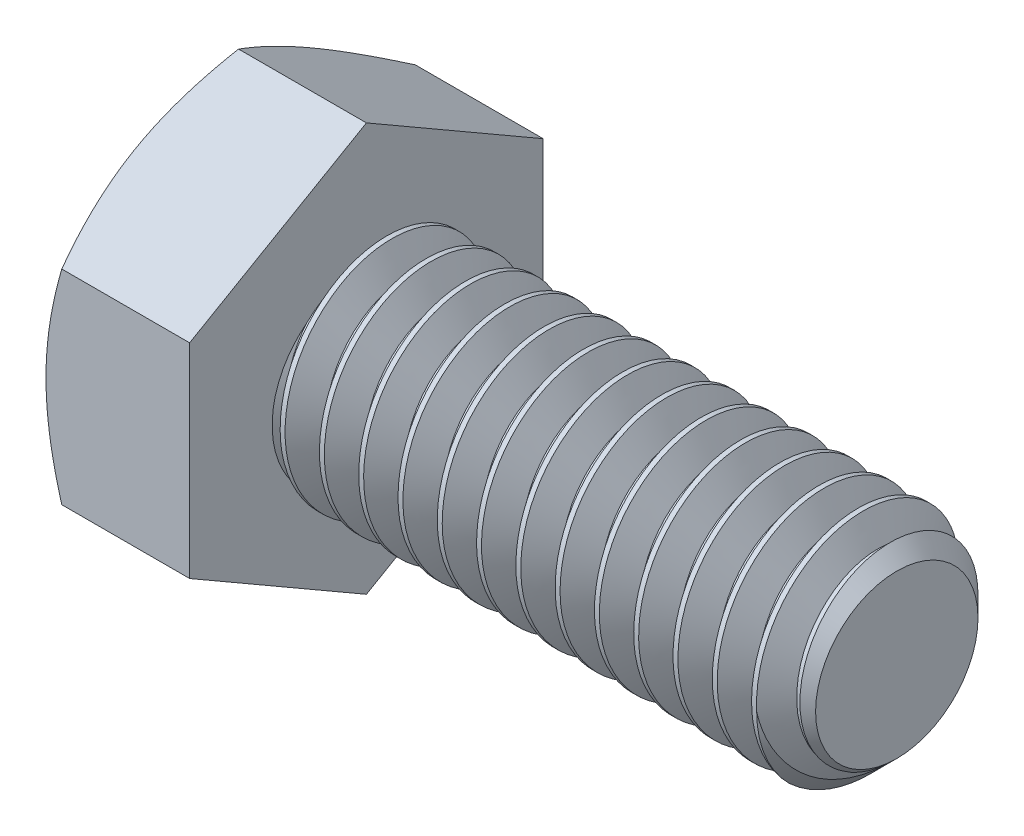
SolidWorks part; units mm, degrees
note: '?' marks a value the reader was unsure of.
ref_plane "Front Plane" through (0, 0, 0) normal (0, 0, 1) x (1, 0, 0)
ref_plane "Top Plane" through (0, 0, 0) normal (0, 1, 0) x (1, 0, 0)
ref_plane "Right Plane" through (0, 0, 0) normal (1, 0, 0) x (0, 0, -1)
sketch "Sketch1" plane through (0, 0, 0) normal (0, 0, 1) x (1, 0, 0)
  line L0 (-12.1047, 0) -> (12.1047, 0) construction
  line L1 (12.1047, 3.9751) -> (12.1047, -3.9751) construction
  line L2 (-6.9453, 6.35) -> (-6.9453, -6.35) construction
  line L3 (-12.1047, 6.35) -> (-12.1047, -6.35) construction
  line L4 (12.1047, 3.9751) -> (13.5158, 3.9751)
  point P9 (-6.9453, 0)
  point P10 (7.1658, -3.9751)
  point P12 (-12.1047, 6.35)
  point P13 (-6.9453, 6.35)
  point P14 (12.1047, 3.9751)
  dimension "Screw Size Decimal Equivalent" = 7.9502
  dimension "Head Width" = 12.7
  dimension "Head Height" = 5.1594
  dimension "Length" = 19.05
  dimension "D1" = 4.9389
  dimension "Thread Size" = 7.9502
  dimension "Pitch" = 1.4111
ref_plane "Plane2" through (12.1047, 0, 0) normal (1, 0, 0) x (0, 0, -1)
sketch "Sketch5" plane through (12.1047, 0, 0) normal (1, 0, 0) x (0, 0, -1)
  circle A0 centre (0, 0) radius 3.9751
extrude "Boss-Extrude3" add sketch "Sketch5" against normal up to vertex (19.05 mm away) up to point (-6.9453, 0, 0)
sketch "Sketch9" plane through (12.1047, 0, 0) normal (1, 0, 0) x (0, 0, -1)
  circle A1 centre (0, 0) radius 3.9751
  circle A2 centre (0, 0) radius 3.9751
  dimension "D1" = 0
curve "Helix/Spiral1" pitch 1.4111 height 20.4611 turns 14.5 parameters "Pitch"=1.4111
chamfer "Chamfer1" distance 1.0583 angle 45 1 edges at (12.1047, 0, -3.9751)
sketch "Sketch11" plane through (-6.9453, 0, 0) normal (-1, 0, 0) x (0, 0, 1)
  line L1 (0, 7.3323) -> (-6.35, 3.6662)
  line L2 (-6.35, 3.6662) -> (-6.35, -3.6662)
  line L3 (-6.35, -3.6662) -> (0, -7.3323)
  line L4 (0, -7.3323) -> (6.35, -3.6662)
  line L5 (6.35, -3.6662) -> (6.35, 3.6662)
  line L6 (6.35, 3.6662) -> (0, 7.3323)
  circle A0 centre (0, 0) radius 6.35 construction
extrude "Boss-Extrude4" add sketch "Sketch11" along normal up to vertex (5.1594 mm away) up to point (-12.1047, -6.35, 0)
sketch "Sketch12" plane through (-12.1047, 0, 0) normal (-1, 0, 0) x (0, 0, 1)
  circle A0 centre (0, 0) radius 6.35 construction
  circle A1 centre (0, 0) radius 6.35
extrude "Cut-Extrude1" cut sketch "Sketch12" against normal through all draft 60 flip side to cut
sketch "Sketch14" plane through (-12.1047, 0, 0) normal (-1, 0, 0) x (0, 0, 1)
  line L0 (-6.35, 3.6662) -> (6.35, 3.6662) construction
  point P5 (-6.35, 3.6662)
  point P6 (6.35, 3.6662)
sketch "Sketch15" plane through (0, 0, 0) normal (0, 0, 1) x (1, 0, 0)
  point P0 (-6.9453, 7.3323)
  point P1 (-12.1047, 6.35)
  point P3 (12.1047, 2.9168)
ref_axis "Center Axis" through (-29.9493, 0, 0) along (1, 0, 0)?
sketch "Sketch10" plane through (0, 0, 0) normal (0, 0, 1) x (1, 0, 0)
  line L0 (12.1047, 3.9751) -> (12.6339, 3.0586)
  line L1 (12.6339, 3.0586) -> (12.8102, 3.0586)
  line L2 (12.8102, 3.0586) -> (13.3394, 3.9751)
  line L3 (12.1047, 3.9751) -> (13.3394, 3.9751)
  line L4 (12.722, 3.9751) -> (12.722, 3.0586) construction
  line L5 (12.3693, 3.5168) -> (13.0748, 3.5168) construction
  dimension "D1" = 60
  dimension "D2" = 0.1764
  dimension "D3" = 0.7056
sweep "Cut-Sweep1" cut profiles "Sketch10" path "Helix/Spiral1"
sketch "Sketch13" plane through (-6.9453, 0, 0) normal (1, 0, 0) x (0, 0, -1)
  line L6 (0, 7.3323) -> (-6.35, 3.6662)
  line L7 (-6.35, 3.6662) -> (-6.35, -3.6662)
  line L8 (-6.35, -3.6662) -> (0, -7.3323)
  line L9 (0, -7.3323) -> (6.35, -3.6662)
  line L10 (6.35, -3.6662) -> (6.35, 3.6662)
  line L11 (6.35, 3.6662) -> (0, 7.3323)
  line L12 (0, 7.3323) -> (-6.35, 3.6662)
  line L13 (-6.35, 3.6662) -> (-6.35, -3.6662)
  line L14 (-6.35, -3.6662) -> (0, -7.3323)
  line L15 (0, -7.3323) -> (6.35, -3.6662)
  line L16 (6.35, -3.6662) -> (6.35, 3.6662)
  line L17 (6.35, 3.6662) -> (0, 7.3323)
  dimension "D1" = 0
extrude "Boss-Extrude5" add sketch "Sketch13" against normal up to vertex (4.5922 mm away) up to point (-11.5375, 3.6662, 6.35)
equation "\"D2@Sketch10\" = \"Pitch@Sketch1\" * .125"
equation "\"D3@Sketch10\" = \"Pitch@Sketch1\" * .5"
equation "\"D3@Helix/Spiral1\" = \"Length@Sketch1\" + \"Pitch@Sketch1\""
equation "\"D1@Chamfer1\" = \"Pitch@Sketch1\" * .75"
equation "\"D1@Sketch1\" = \"Pitch@Sketch1\" * 3.5"
equation "\"Pitch@Helix/Spiral1\"=\"Pitch@Sketch1\""
